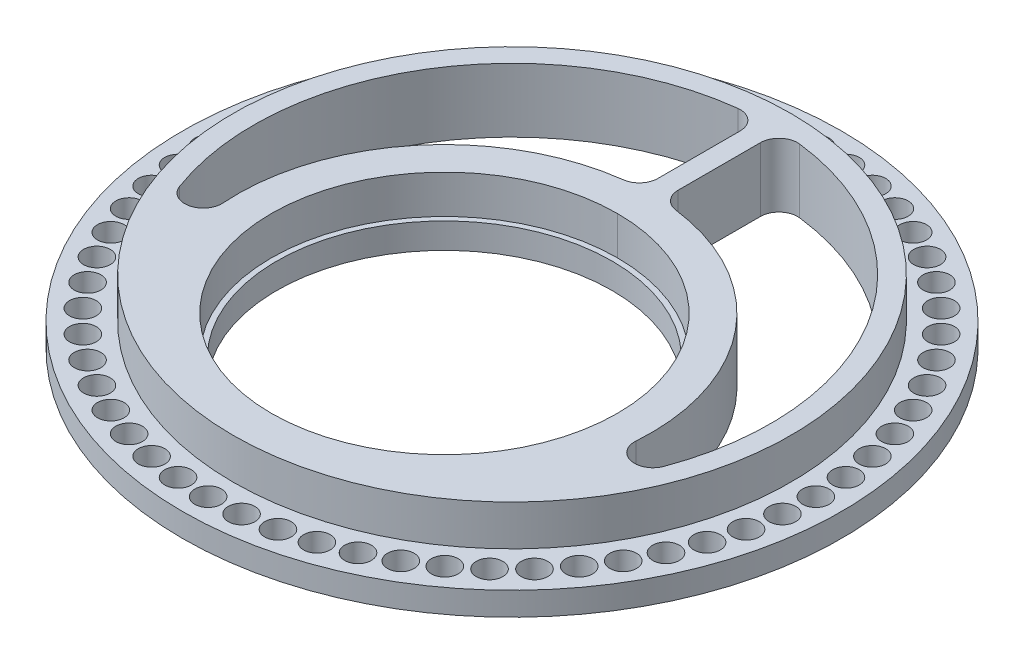
SolidWorks part; units mm, degrees
material "6061-T6 (SS)"
ref_plane "X-Y Datum" through (0, 0, 0) normal (0, 0, 1) x (1, 0, 0)
ref_plane "X-Z Datum" through (0, 0, 0) normal (0, 1, 0) x (1, 0, 0)
ref_plane "Y-Z Datum" through (0, 0, 0) normal (1, 0, 0) x (0, 0, -1)
sketch "Sketch1" plane through (0, 0, 0) normal (0, 1, 0) x (1, 0, 0)
  line L0 (0, 0) -> (0, -12.7) construction
  line L1 (0, -43.0151) -> (0, 43.0151) construction
  line L2 (0, 52.3875) -> (0, 64.4525) construction
  circle A0 centre (0, -12.7) radius 30.988
  circle A1 centre (0, 0) radius 52.3875 construction
  circle A2 centre (0, 0) radius 64.4525
  circle A3 centre (0, 0) radius 58.42 construction
  point P12 (0, 58.42)
  dimension "D2" = 61.976
  dimension "D3" = 104.775
  dimension "D4" = 128.905
  dimension "D5" = 116.84
  dimension "D1" = 12.7
extrude "Slotted-Body Extrude" add sketch "Sketch1" along normal blind 4.191 and the other way blind 0.2032
sketch "Sketch5" plane through (0, 4.191, 0) normal (0, 1, 0) x (1, 0, 0)
  circle A0 centre (0, 0) radius 52.3875 construction
  circle A1 centre (0, 0) radius 52.3875
extrude "Boss-Extrude3" add sketch "Sketch5" along normal blind 7.62
sketch "Sketch6" plane through (0, -0.2032, 0) normal (0, -1, 0) x (1, 0, 0)
  line L0 (0, -79.2756) -> (0, 0) construction
  circle A0 centre (0, 12.7) radius 30.988 construction
  circle A1 centre (0, 12.7) radius 30.988 construction
  circle A2 centre (0, 12.7) radius 32.512
  circle A21 centre (0, 0) radius 64.4525 construction
  dimension "D1" = 65.024
extrude "Cut-Extrude5" cut sketch "Sketch6" against normal through all
sketch "Sketch8" plane through (0, -0.2032, 0) normal (0, -1, 0) x (1, 0, 0)
  circle A0 centre (0, 12.7) radius 32.512 construction
  circle A1 centre (0, 12.7) radius 32.512
  circle A2 centre (0, 12.7) radius 31.496
  dimension "D1" = 62.992
extrude "Boss-Extrude4" add sketch "Sketch8" against normal blind 4.795 separate body
ref_point "Point1"
ref_plane "Plane1" through (0, 0, 0) normal (1, 0, 0) x (0, 0, -1)
split line "Split Line1"
sketch "Sketch11" plane through (0, -0.2032, 0) normal (0, -1, 0) x (1, 0, 0)
  line L1 (-64.4525, -64.4525) -> (64.4525, -64.4525)
  line L2 (-64.4525, -64.4525) -> (-64.4525, 64.4525)
  line L3 (-64.4525, 64.4525) -> (64.4525, 64.4525)
  line L4 (64.4525, -64.4525) -> (64.4525, 64.4525)
  line L5 (-64.4525, -64.4525) -> (64.4525, 64.4525) construction
  line L6 (-64.4525, 64.4525) -> (64.4525, -64.4525) construction
  circle A0 centre (0, 0) radius 64.4525 construction
  point P0 (0, 0)
ref_point "Point6"
sketch "Sketch12" plane through (0, 4.191, 0) normal (0, 1, 0) x (1, 0, 0)
  line L0 (0, 0) -> (-1.0196, -58.4111) construction
  line L1 (0, 0) -> (-50.0757, -30.0885) construction
  line L2 (0, 0) -> (0, -64.4525) construction
  arc A3 (-50.0757, -30.0885) -> (-1.0196, -58.4111) centre (0, 0) ccw construction
  arc A10 (-51.0166, -34.6728) -> (-4.5192, -61.5181) centre (0, 0) ccw
  arc A15 (-45.6177, -31.0035) -> (-4.041, -55.0079) centre (0, 0) ccw
  arc A20 (-45.6177, -31.0035) -> (-51.0166, -34.6728) centre (-48.3172, -32.8382) ccw
  arc A25 (-52.8734, -31.7696) -> (-1.0765, -61.6745) centre (0, 0) ccw construction
  arc A30 (-47.278, -28.4075) -> (-0.9626, -55.1477) centre (0, 0) ccw construction
  arc A35 (-4.5192, -61.5181) -> (-4.041, -55.0079) centre (-4.2801, -58.263) ccw
  circle A40 centre (0, 0) radius 64.4525 construction
  arc A45 (-55.5359, -26.8453) -> (-49.6587, -24.0043) centre (-52.5973, -25.4248) ccw
  arc A50 (-49.6587, 24.0043) -> (-49.6587, -24.0043) centre (0, 0) ccw
  arc A55 (-49.6587, 24.0043) -> (-55.5359, 26.8453) centre (-52.5973, 25.4248) ccw
  arc A56 (-55.5359, 26.8453) -> (-55.5359, -26.8453) centre (0, 0) ccw
  arc A57 (-51.0166, 34.6728) -> (-45.6177, 31.0035) centre (-48.3172, 32.8382) ccw
  arc A58 (-4.041, 55.0079) -> (-45.6177, 31.0035) centre (0, 0) ccw
  arc A59 (-4.041, 55.0079) -> (-4.5192, 61.5181) centre (-4.2801, 58.263) ccw
  arc A60 (-4.5192, 61.5181) -> (-51.0166, 34.6728) centre (0, 0) ccw
  arc A61 (4.5192, 61.5181) -> (4.041, 55.0079) centre (4.2801, 58.263) ccw
  arc A62 (45.6177, 31.0035) -> (4.041, 55.0079) centre (0, 0) ccw
  arc A63 (45.6177, 31.0035) -> (51.0166, 34.6728) centre (48.3172, 32.8382) ccw
  arc A64 (51.0166, 34.6728) -> (4.5192, 61.5181) centre (0, 0) ccw
  arc A65 (55.5359, 26.8453) -> (49.6587, 24.0043) centre (52.5973, 25.4248) ccw
  arc A66 (49.6587, -24.0043) -> (49.6587, 24.0043) centre (0, 0) ccw
  arc A67 (49.6587, -24.0043) -> (55.5359, -26.8453) centre (52.5973, -25.4248) ccw
  arc A68 (55.5359, -26.8453) -> (55.5359, 26.8453) centre (0, 0) ccw
  arc A69 (51.0166, -34.6728) -> (45.6177, -31.0035) centre (48.3172, -32.8382) ccw
  arc A70 (4.041, -55.0079) -> (45.6177, -31.0035) centre (0, 0) ccw
  arc A71 (4.041, -55.0079) -> (4.5192, -61.5181) centre (4.2801, -58.263) ccw
  arc A72 (4.5192, -61.5181) -> (51.0166, -34.6728) centre (0, 0) ccw
  point P57 (0, 0)
  dimension "D1" = 116.84
  dimension "D2" = 58
  dimension "D5" = 1
  dimension "D3" = 3.2639
  dimension "D4" = 3.2639
sketch "Sketch16" plane through (0, 11.811, 0) normal (0, 1, 0) x (1, 0, 0)
  line L0 (0, 0) -> (0, 48.5775) construction
  line L4 (1.905, 44.7607) -> (1.905, 29.3092)
  line L5 (-1.905, 44.7607) -> (-1.905, 29.3092)
  arc A22 (45.517, -16.9698) -> (5.8156, 48.2281) centre (0, 0) ccw
  circle A23 centre (0, -12.7) radius 32.512 construction
  arc A24 (38.7611, -15.4983) -> (4.9524, 25.8451) centre (0, -12.7) ccw
  arc A25 (-38.7611, -15.4983) -> (-45.517, -16.9698) centre (-42.2446, -15.7497) cw
  arc A28 (45.517, -16.9698) -> (38.7611, -15.4983) centre (42.2446, -15.7497) cw
  circle A31 centre (0, 0) radius 52.3875 construction
  arc A32 (-5.8156, 48.2281) -> (-45.517, -16.9698) centre (0, 0) ccw
  arc A33 (-4.9524, 25.8451) -> (-38.7611, -15.4983) centre (0, -12.7) ccw
  arc A39 (4.9524, 25.8451) -> (1.905, 29.3092) centre (5.3975, 29.3092) cw
  arc A45 (1.905, 44.7607) -> (5.8156, 48.2281) centre (5.3975, 44.7607) cw
  arc A46 (-4.9524, 25.8451) -> (-1.905, 29.3092) centre (-5.3975, 29.3092) ccw
  arc A47 (-1.905, 44.7607) -> (-5.8156, 48.2281) centre (-5.3975, 44.7607) ccw
  point P18 (1.905, 26.1153)
  point P21 (1.905, 48.5401)
  point P24 (-1.905, 26.1153)
  point P27 (-1.905, 48.5401)
  dimension "D1" = 3.4925
  dimension "D2" = 3.4925
  dimension "D3" = 65.024
  dimension "D4" = 6.35
  dimension "D5" = 3.81
  dimension "D6" = 1.905
  dimension "D7" = 3.4925
extrude "Cut-Extrude6" cut sketch "Sketch16" against normal through all contours L5 A47 A32 A25 A33 A46 | A45 L4 A39 A24 A28 A22 | A46 L5 A47 A32 A25 A33 region at (27.5566, 11.811, -21.5451) region at (-27.5566, 11.811, -21.5451)
other "Move Face1" flip direction yes face at (0, -0.2032, 64.4525) offset 2.54 parameters "D1"=2.54
sketch "Sketch18" plane through (0, 4.191, 0) normal (0, 1, 0) x (1, 0, 0)
  line L0 (0, 52.3875) -> (0, 61.7844) construction
  circle A0 centre (0, 0) radius 52.3875 construction
  circle A1 centre (0, 0) radius 52.3875 construction
  circle A2 centre (0, 57.0859) radius 2.5
  dimension "D1" = 5
extrude "Cut-Extrude7" cut sketch "Sketch18" against normal through all
pattern_circular "CirPattern1" count 60 over 360 about axis through (0, 4.191, 0) along (0, 1, 0) of "Cut-Extrude7"
